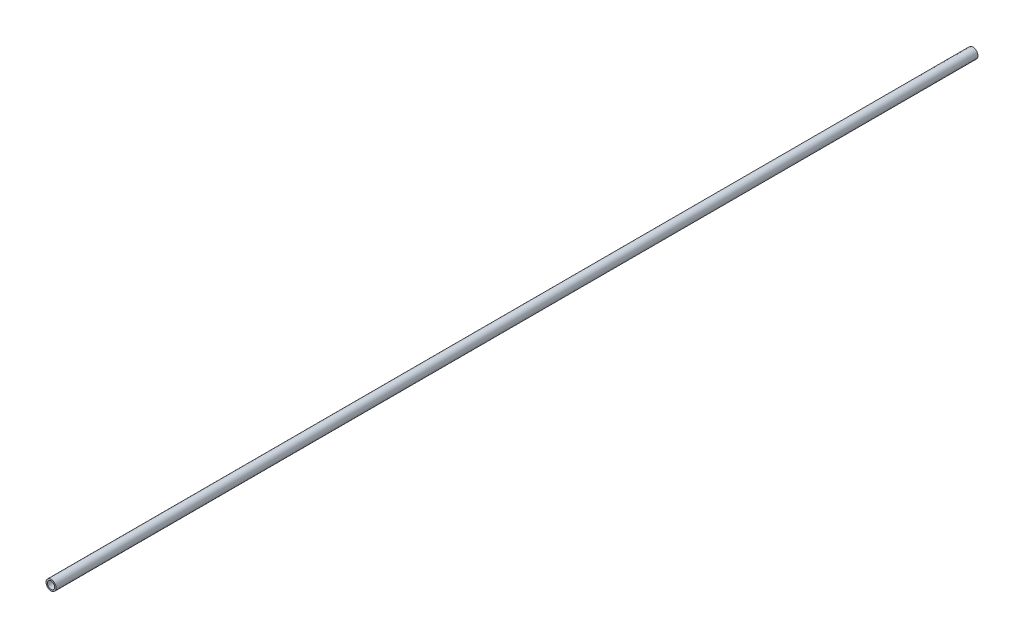
SolidWorks part; units mm, degrees
ref_plane "Front Plane" through (0, 0, 0) normal (0, 0, 1) x (1, 0, 0)
ref_plane "Top Plane" through (0, 0, 0) normal (0, 1, 0) x (1, 0, 0)
ref_plane "Right Plane" through (0, 0, 0) normal (1, 0, 0) x (0, 0, -1)
sketch "Sketch1" plane through (0, 0, 0) normal (0, 0, 1) x (1, 0, 0)
  circle A0 centre (0, 0) radius 16.7005
  dimension "Pipe OD" = 33.401
extrude "Extrude-Thin1" add sketch "Sketch1" along normal mid plane 3048 thin thin type one direction reverse wall 4.5466
